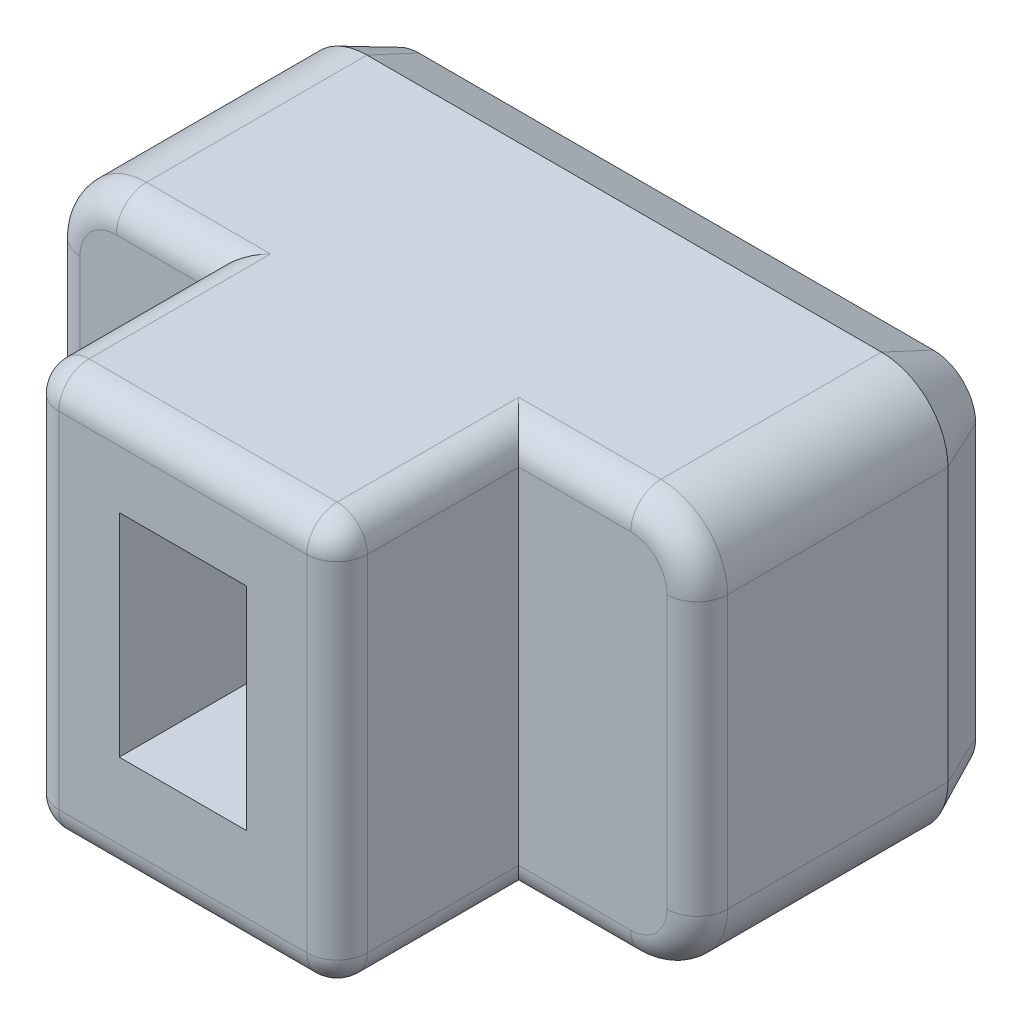
SolidWorks part; units mm, degrees
ref_plane "Plan de face" through (0, 0, 0) normal (0, 0, 1) x (1, 0, 0)
ref_plane "Plan de dessus" through (0, 0, 0) normal (0, 1, 0) x (1, 0, 0)
ref_plane "Plan de droite" through (0, 0, 0) normal (1, 0, 0) x (0, 0, -1)
sketch "Esquisse2" plane through (0, 0, 0) normal (0, 0, 1) x (1, 0, 0)
  line L1 (1.1, 0) -> (9.6, 0)
  line L2 (0, 1.1) -> (0, 5.6)
  line L3 (1.1, 6.7) -> (9.6, 6.7)
  line L4 (10.7, 1.1) -> (10.7, 5.6)
  arc A0 (9.6, 6.7) -> (10.7, 5.6) centre (9.6, 5.6) cw
  arc A1 (9.6, 0) -> (10.7, 1.1) centre (9.6, 1.1) ccw
  arc A2 (1.1, 0) -> (0, 1.1) centre (1.1, 1.1) cw
  arc A3 (0, 5.6) -> (1.1, 6.7) centre (1.1, 5.6) cw
  point P7 (10.7, 6.7)
  point P12 (0, 0)
  point P15 (0, 6.7)
  dimension "D3" = 1.1
  dimension "D1" = 10.7
  dimension "D2" = 6.7
extrude "Boss.-Extru.1" add sketch "Esquisse2" along normal blind 8
sketch "Esquisse3" plane through (0, 0, 8) normal (0, 0, 1) x (1, 0, 0)
  line L0 (0, 5.6) -> (0, 1.1) construction
  line L1 (4.15, 5.25) -> (6.25, 5.25)
  line L2 (4.15, 5.25) -> (4.15, 1.75)
  line L3 (4.15, 1.75) -> (6.25, 1.75)
  line L4 (6.25, 5.25) -> (6.25, 1.75)
  line L5 (10.7, 1.1) -> (10.7, 5.6) construction
  line L6 (9.6, 6.7) -> (1.1, 6.7) construction
  line L7 (1.1, 0) -> (9.6, 0) construction
  dimension "D1" = 2.1
  dimension "D2" = 3.5
  dimension "D3" = 4.15
  dimension "D4" = 4.45
  dimension "D5" = 1.45
  dimension "D6" = 1.75
extrude "Enlèv. mat.-Extru.1" cut sketch "Esquisse3" against normal blind 3
sketch "Esquisse4" plane through (0, 0, 8) normal (0, 0, 1) x (1, 0, 0)
  line L0 (2.65, 6.7) -> (2.65, 0)
  line L1 (9.6, 6.7) -> (1.1, 6.7) construction
  line L2 (1.1, 0) -> (9.6, 0) construction
  line L3 (2.65, 0) -> (7.75, 0)
  line L4 (7.75, 0) -> (7.75, 6.7)
  line L5 (7.75, 6.7) -> (2.65, 6.7)
  line L6 (4.15, 5.25) -> (4.15, 1.75) construction
  line L7 (6.25, 1.75) -> (6.25, 5.25) construction
  dimension "D1" = 1.5
  dimension "D2" = 1.5
extrude "Enlèv. mat.-Extru.2" cut sketch "Esquisse4" against normal blind 3 flip side to cut
fillet "Congé1" radius 0.5 18 edges at (8.675, 0, 5) (10.3778, 0.3222, 5) (10.7, 3.35, 5) (10.3778, 6.3778, 5) (1.875, 6.7, 5) (0.3222, 6.3778, 5) (1.875, 0, 5) (0.3222, 0.3222, 5) (7.75, 6.7, 6.5) (2.65, 6.7, 6.5) (7.75, 0, 6.5) (2.65, 0, 6.5) (2.65, 3.35, 8) (5.2, 6.7, 8) (7.75, 3.35, 8) (5.2, 0, 8) (8.675, 6.7, 5) (0, 3.35, 5)
chamfer "Chanfrein1" distance 0.4 angle 65 8 edges at (5.35, 0, 0) (10.3778, 0.3222, 0) (0.3222, 0.3222, 0) (10.7, 3.35, 0) (0, 3.35, 0) (10.3778, 6.3778, 0) (0.3222, 6.3778, 0) (5.35, 6.7, 0) first distance on face at (5.35, 3.35, 0)
ref_plane "Plan1" through (0, 0, 0.2) normal (0, 0, 1) x (1, 0, 0)
sketch "Esquisse5" plane through (0, 0, 0.2) normal (0, 0, 1) x (1, 0, 0)
  line L0 (-0.856, 5.5947) -> (11.6517, 5.5947) construction
  text T0 "AP" font "Century Gothic" height 4.5
extrude "Enlèv. mat.-Extru.3" cut sketch "Esquisse5" against normal blind 0.3
extrude "Boss.-Extru.2" add sketch "Esquisse5<3>" against normal blind 0.2 from offset 0.2 offset against normal yes
sketch "Esquisse5<3>" plane through (0, 0, 0.2) normal (0, 0, 1) x (1, 0, 0) same geometry as "Esquisse5"
